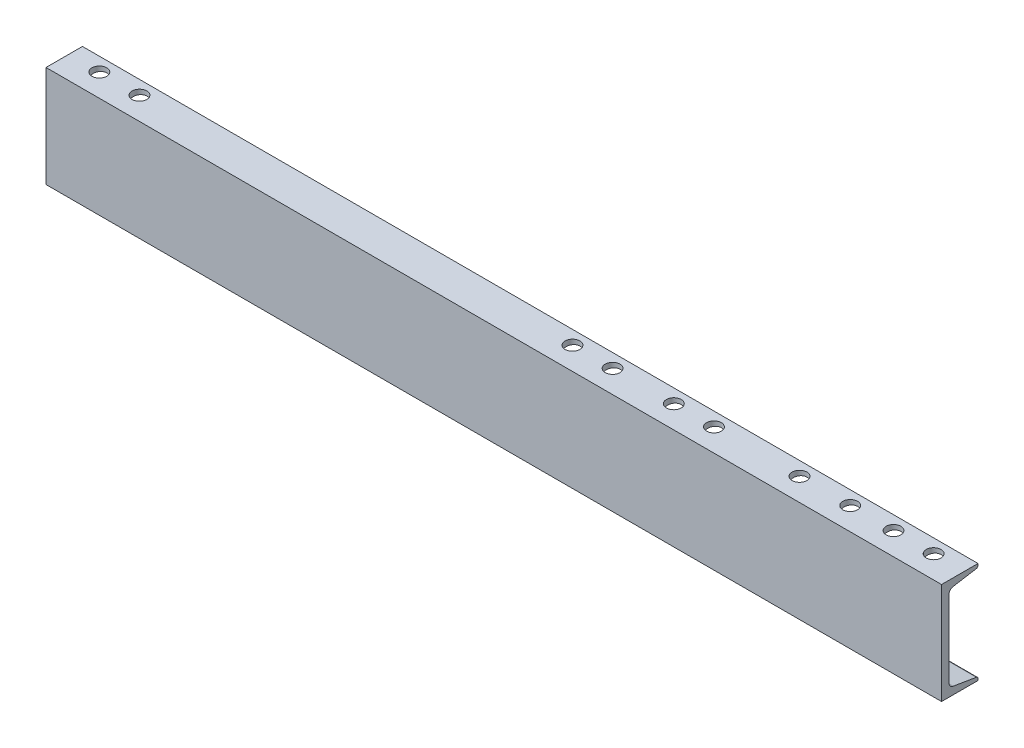
SolidWorks part; units mm, degrees
ref_plane "Front Plane" through (0, 0, 0) normal (0, 0, 1) x (1, 0, 0)
ref_plane "Top Plane" through (0, 0, 0) normal (0, 1, 0) x (1, 0, 0)
ref_plane "Right Plane" through (0, 0, 0) normal (1, 0, 0) x (0, 0, -1)
sketch "Sketch1" plane through (0, 0, 0) normal (1, 0, 0) x (0, 0, -1)
  line L0 (-27.3939, -76.2) -> (-27.3939, 76.2)
  line L1 (-27.3939, 76.2) -> (27.3939, 76.2)
  line L2 (-27.3939, -76.2) -> (27.3939, -76.2)
  line L3 (4.3561, -67.4878) -> (-21.0439, -67.4878) construction
  line L4 (-16.2941, 57.3918) -> (-16.2941, -57.3918)
  line L5 (27.3939, 76.2) -> (27.3939, 73.7107)
  line L6 (27.3939, -76.2) -> (27.3939, -73.7107)
  line L7 (-9.9269, 64.9081) -> (24.847, 70.7042)
  line L8 (-9.9269, -64.9081) -> (24.847, -70.7042)
  arc A0 (-16.2941, -57.3918) -> (-9.9269, -64.9081) centre (-8.6741, -57.3918) ccw
  arc A1 (-16.2941, 57.3918) -> (-9.9269, 64.9081) centre (-8.6741, 57.3918) cw
  arc A2 (27.3939, 73.7107) -> (24.847, 70.7042) centre (24.3459, 73.7107) cw
  arc A3 (27.3939, -73.7107) -> (24.847, -70.7042) centre (24.3459, -73.7107) ccw
extrude "Boss-Extrude1" add sketch "Sketch1" along normal mid plane 1346.2
sketch "Sketch3" plane through (0, 0, 16.2941) normal (0, 0, -1) x (-1, 0, 0)
  line L0 (-431.8, -25.4) -> (-469.9, -25.4) construction
  line L1 (-431.8, -33.3375) -> (-469.9, -33.3375)
  line L2 (-431.8, -17.4625) -> (-469.9, -17.4625)
  line L3 (-673.1, -57.3918) -> (-673.1, 57.3918) construction
  line L4 (30.1333, 0) -> (-30.1333, 0) construction
  line L5 (0, 0) -> (82.55, 0) construction
  line L6 (673.1, -57.3918) -> (673.1, 57.3918) construction
  line L7 (-673.1, 0) -> (-307.7005, 0) construction
  arc A0 (-431.8, -33.3375) -> (-431.8, -17.4625) centre (-431.8, -25.4) ccw
  arc A1 (-469.9, -17.4625) -> (-469.9, -33.3375) centre (-469.9, -25.4) ccw
  circle A2 centre (-593.725, 0) radius 12.7 construction
  circle A3 centre (82.55, 0) radius 9.525
  circle A4 centre (31.75, 0) radius 9.525 construction
  point P3 (-450.85, -25.4)
  dimension "D4" = 25.4
  dimension "D7" = 19.05
  dimension "D8" = 50.8
  dimension "D1" = 15.875
  dimension "D2" = 38.1
  dimension "D3" = 203.2
  dimension "D5" = 79.375
  dimension "D6" = 590.55
  dimension "D9" = 25.4
sketch "Sketch5" plane through (0, -76.2, 0) normal (0, -1, 0) x (1, 0, 0)
  line L0 (687.9131, -6.7373) -> (124.9749, -6.7373) construction
  line L2 (673.1, 27.3939) -> (673.1, -27.3939) construction
  line L3 (-673.1, 27.3939) -> (-673.1, -27.3939) construction
  line L5 (673.1, 27.3939) -> (-673.1, 27.3939) construction
  circle A0 centre (627.0625, -6.7373) radius 11.1125
  circle A1 centre (566.7375, -6.7374) radius 11.1125
  circle A2 centre (296.8625, -6.7373) radius 11.1125
  circle A3 centre (236.5375, -6.7374) radius 11.1125
  circle A4 centre (84.1375, -6.7374) radius 11.1125
  circle A5 centre (144.4625, -6.7373) radius 11.1125
  circle A6 centre (-627.0625, -6.7373) radius 11.1125
  circle A7 centre (-566.7375, -6.7373) radius 11.1125
  circle A8 centre (425.45, -6.7373) radius 11.1125
  circle A9 centre (501.65, -6.7373) radius 11.1125
  dimension "D2" = 22.225
  dimension "D4" = 60.325
  dimension "D12" = 22.225
  dimension "D13" = 22.225
  dimension "D14" = 1098.55
  dimension "D15" = 76.2
  dimension "D3" = 46.0375
  dimension "D6" = 330.2
  dimension "D8" = 482.6
  dimension "D10" = 46.0375
  dimension "D11" = 34.1313
  dimension "D5" = 2
  dimension "D7" = 2
  dimension "D9" = 2
extrude "Cut-Extrude3" cut sketch "Sketch5" against normal up to surface (152.4 mm away) up to face at (0, 76.2, 0)
